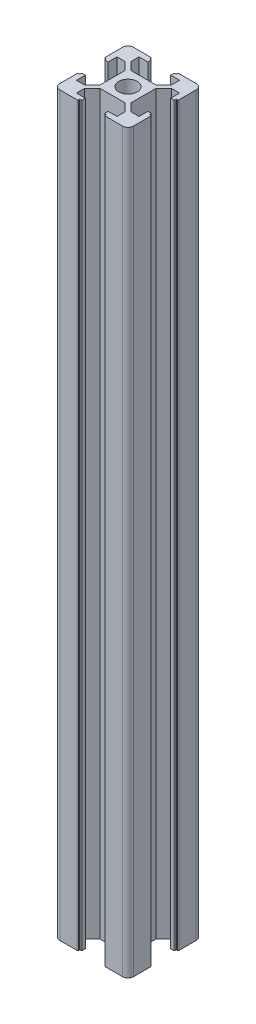
SolidWorks part; units mm, degrees
ref_plane "Front Plane" through (0, 0, 0) normal (0, 0, 1) x (1, 0, 0)
ref_plane "Top Plane" through (0, 0, 0) normal (0, 1, 0) x (1, 0, 0)
ref_plane "Right Plane" through (0, 0, 0) normal (1, 0, 0) x (0, 0, -1)
sketch "Sketch1" plane through (0, 0, 0) normal (0, 1, 0) x (1, 0, 0)
  line L0 (-8.5, 8.5) -> (8.5, 8.5)
  line L1 (-8.5, -10) -> (8.5, -10)
  line L2 (-10, -8.5) -> (-10, 8.5)
  line L3 (-8.5, 10) -> (8.5, 10)
  line L4 (10, -8.5) -> (10, 8.5)
  line L5 (-10, -10) -> (10, 10) construction
  line L6 (-10, 10) -> (10, -10) construction
  line L7 (8.5, -8.5) -> (8.5, 8.5)
  line L8 (-8.5, -8.5) -> (8.5, -8.5)
  line L9 (-8.5, -8.5) -> (-8.5, 8.5)
  line L10 (-10.4243, 9.5757) -> (9.5757, -10.4243)
  line L11 (-9.5757, -10.4243) -> (10.4243, 9.5757)
  line L12 (-9.5757, 10.4243) -> (10.4243, -9.5757)
  line L13 (-10.4243, -9.5757) -> (9.5757, 10.4243)
  line L14 (-9.5, -8.5) -> (-9.5, 8.5)
  line L15 (-10, -5.5) -> (10, -5.5)
  line L16 (-10, -5.5) -> (-10, 5.5)
  line L17 (-10, 5.5) -> (10, 5.5)
  line L18 (10, -5.5) -> (10, 5.5)
  line L19 (-10, -5.5) -> (10, 5.5) construction
  line L20 (-10, 5.5) -> (10, -5.5) construction
  line L21 (5.5, -10) -> (-5.5, -10)
  line L22 (5.5, -10) -> (5.5, 10)
  line L23 (5.5, 10) -> (-5.5, 10)
  line L24 (-5.5, -10) -> (-5.5, 10)
  line L25 (5.5, -10) -> (-5.5, 10) construction
  line L26 (5.5, 10) -> (-5.5, -10) construction
  line L27 (10, -3.1) -> (-10, -3.1)
  line L28 (10, -3.1) -> (10, 3.1)
  line L29 (10, 3.1) -> (-10, 3.1)
  line L30 (-10, -3.1) -> (-10, 3.1)
  line L31 (10, -3.1) -> (-10, 3.1) construction
  line L32 (10, 3.1) -> (-10, -3.1) construction
  line L33 (10, -3.6) -> (-10, -3.6)
  line L34 (10, -3.6) -> (10, 3.6)
  line L35 (10, 3.6) -> (-10, 3.6)
  line L36 (-10, -3.6) -> (-10, 3.6)
  line L37 (10, -3.6) -> (-10, 3.6) construction
  line L38 (10, 3.6) -> (-10, -3.6) construction
  line L39 (-8.5, 9.5) -> (8.5, 9.5)
  line L40 (9.5, -8.5) -> (9.5, 8.5)
  line L41 (-8.5, -9.5) -> (8.5, -9.5)
  arc A0 (-8.5, 10) -> (-10, 8.5) centre (-8.5, 8.5) ccw
  arc A1 (10, 8.5) -> (8.5, 10) centre (8.5, 8.5) ccw
  arc A2 (8.5, -10) -> (10, -8.5) centre (8.5, -8.5) ccw
  arc A3 (-10, -8.5) -> (-8.5, -10) centre (-8.5, -8.5) ccw
  arc A4 (8.5, 8.5) -> (8.5, 8.5) centre (8.5, 8.5) ccw
  arc A5 (8.5, -8.5) -> (8.5, -8.5) centre (8.5, -8.5) ccw
  arc A6 (-8.5, -8.5) -> (-8.5, -8.5) centre (-8.5, -8.5) ccw
  arc A7 (-8.5, 8.5) -> (-8.5, 8.5) centre (-8.5, 8.5) ccw
  circle A8 centre (0, 0) radius 2.5
  arc A9 (-8.5, 9.5) -> (-9.5, 8.5) centre (-8.5, 8.5) ccw
  arc A10 (9.5, 8.5) -> (8.5, 9.5) centre (8.5, 8.5) ccw
  arc A11 (8.5, -9.5) -> (9.5, -8.5) centre (8.5, -8.5) ccw
  arc A12 (-9.5, -8.5) -> (-8.5, -9.5) centre (-8.5, -8.5) ccw
  point P0 (0, 0)
  point P38 (0, 0)
  point P43 (0, 0)
  dimension "D3" = 1.5
  dimension "D4" = 1.5
  dimension "D5" = 1.5
  dimension "D6" = 1.5
  dimension "D12" = 5
  dimension "D1" = 20
  dimension "D2" = 20
  dimension "D10" = 11
  dimension "D11" = 11
  dimension "D13" = 6.2
  dimension "D14" = 7.2
  dimension "D7" = 1.5
  dimension "D8" = 0.6
  dimension "D9" = 0.6
  dimension "D15" = 0.5
sketch "Sketch2" plane through (0, 0, 0) normal (0, 1, 0) x (1, 0, 0)
  line L0 (-10, -8.5) -> (-10, 8.5) construction
  line L1 (-8.5, 10) -> (8.5, 10) construction
  line L2 (10, -8.5) -> (10, 8.5) construction
  line L3 (-8.5, -10) -> (8.5, -10) construction
  line L4 (-10, -8.5) -> (-10, 8.5)
  line L5 (-8.5, 10) -> (8.5, 10)
  line L6 (10, -8.5) -> (10, 8.5)
  line L7 (-8.5, -10) -> (8.5, -10)
  arc A0 (-8.5, 10) -> (-10, 8.5) centre (-8.5, 8.5) ccw construction
  arc A1 (10, 8.5) -> (8.5, 10) centre (8.5, 8.5) ccw construction
  arc A2 (8.5, -10) -> (10, -8.5) centre (8.5, -8.5) ccw construction
  arc A3 (-10, -8.5) -> (-8.5, -10) centre (-8.5, -8.5) ccw construction
  arc A4 (-8.5, 10) -> (-10, 8.5) centre (-8.5, 8.5) ccw
  arc A5 (10, 8.5) -> (8.5, 10) centre (8.5, 8.5) ccw
  arc A6 (8.5, -10) -> (10, -8.5) centre (8.5, -8.5) ccw
  arc A7 (-10, -8.5) -> (-8.5, -10) centre (-8.5, -8.5) ccw
extrude "Boss-Extrude1" add sketch "Sketch2" along normal blind 200
sketch "Sketch3" plane through (0, 200, 0) normal (0, 1, 0) x (1, 0, 0)
  line L3 (4.2, -4.2) -> (-4.2, -4.2)
  line L4 (4.2, -4.2) -> (4.2, 4.2)
  line L5 (4.2, 4.2) -> (-4.2, 4.2)
  line L6 (-4.2, -3.3515) -> (-4.2, 3.3515)
  line L7 (4.2, -4.2) -> (-4.2, 4.2) construction
  line L8 (4.2, 4.2) -> (-4.2, -4.2) construction
  line L10 (-10.4243, 9.5757) -> (9.5757, -10.4243) construction
  line L11 (-9.5757, 10.4243) -> (10.4243, -9.5757) construction
  line L12 (-10.4243, 9.5757) -> (-4.2, 3.3515)
  line L13 (-9.5757, 10.4243) -> (10.4243, -9.5757)
  line L15 (-8.5, -8.5) -> (-8.5, 8.5) construction
  line L16 (-8.5, -8.5) -> (-8.5, -3.1)
  line L17 (-10, 5.5) -> (10, 5.5) construction
  line L19 (10, -3.1) -> (-10, -3.1) construction
  line L20 (10, -3.6) -> (-10, -3.6) construction
  line L22 (10, 3.6) -> (-10, 3.6) construction
  line L23 (-10, -8.5) -> (-10, 8.5) construction
  line L24 (-10.4243, -9.5757) -> (9.5757, 10.4243) construction
  line L25 (-8.5, 5.5) -> (10, 5.5)
  line L26 (-10, -5.5) -> (10, -5.5) construction
  line L27 (10, -3.1) -> (-4.2, -3.1)
  line L28 (10, -3.6) -> (-4.4485, -3.6)
  line L29 (-10, -5.5) -> (10, -5.5)
  line L30 (10, 3.6) -> (-4.4485, 3.6)
  line L31 (-10, -8.5) -> (-10, -3.8)
  line L32 (-10.4243, -9.5757) -> (-4.2, -3.3515)
  line L33 (-10, 3.8) -> (-10, 8.5)
  line L34 (10, 3.1) -> (-10, 3.1) construction
  line L35 (10, 3.1) -> (-4.2, 3.1)
  line L36 (-9.5, -3.6) -> (-9.8, -3.6)
  line L37 (-8.5, -3.1) -> (-9.3, -3.1)
  line L38 (-9.5, 3.3) -> (-9.5, 3.6)
  line L39 (-8.5, 3.1) -> (-8.5, 8.5)
  line L40 (-9.5, 3.6) -> (-9.8, 3.6)
  line L41 (-9.5, -3.6) -> (-9.5, -3.3)
  line L42 (4.6515, -5.5) -> (10, -5.5)
  line L43 (-8.5, 3.1) -> (-9.3, 3.1)
  line L44 (-9.5, -8.5) -> (-9.5, 8.5) construction
  line L45 (-10, -8.5) -> (-10, 8.5)
  arc A0 (-9.8, -3.6) -> (-10, -3.8) centre (-9.8, -3.8) ccw
  arc A1 (-9.3, -3.1) -> (-9.5, -3.3) centre (-9.3, -3.3) ccw
  arc A2 (-9.5, 3.3) -> (-9.3, 3.1) centre (-9.3, 3.3) ccw
  arc A3 (-10, 3.8) -> (-9.8, 3.6) centre (-9.8, 3.8) ccw
  circle A6 centre (0, 0) radius 2.5 construction
  circle A7 centre (0, 0) radius 2.5
  point P0 (0, 0)
  point P55 (-9.5, 3.1)
  line M12 (-10, 8.5) -> (-10, -8.5)
  dimension "D2" = 0.2
  dimension "D3" = 0.2
  dimension "D4" = 0.2
  dimension "D5" = 0.2
  dimension "D7" = 4.3
extrude "Cut-Extrude1" cut sketch "Sketch3" against normal through all contours L39 L43 L38 L40 L36 L41 L37 L16 L29 L32 L6 L12 L25 M12 | L13 A7 | L13 A7 region at (-7.0241, 200, 0) region at (-0.5269, 200, 0.5269) region at (0.9842, 200, -0.9842)
ref_axis "Axis1" through (0, -20, 0) along (0, 1, 0)
pattern_circular "CirPattern1" count 4 over 360 about axis through (0, -20, 0) along (0, 1, 0) of "Cut-Extrude1"
sketch "Sketch4" plane through (0, 200, 0) normal (0, 1, 0) x (1, 0, 0)
sketch "Sketch5" plane through (0, 200, 0) normal (0, 1, 0) x (1, 0, 0)
  line L0 (-8.5, 3.1) -> (-9.3, 3.1) construction
  line L1 (-8.5, -3.1) -> (-9.3, -3.1) construction
  dimension "D1" = 6.2
